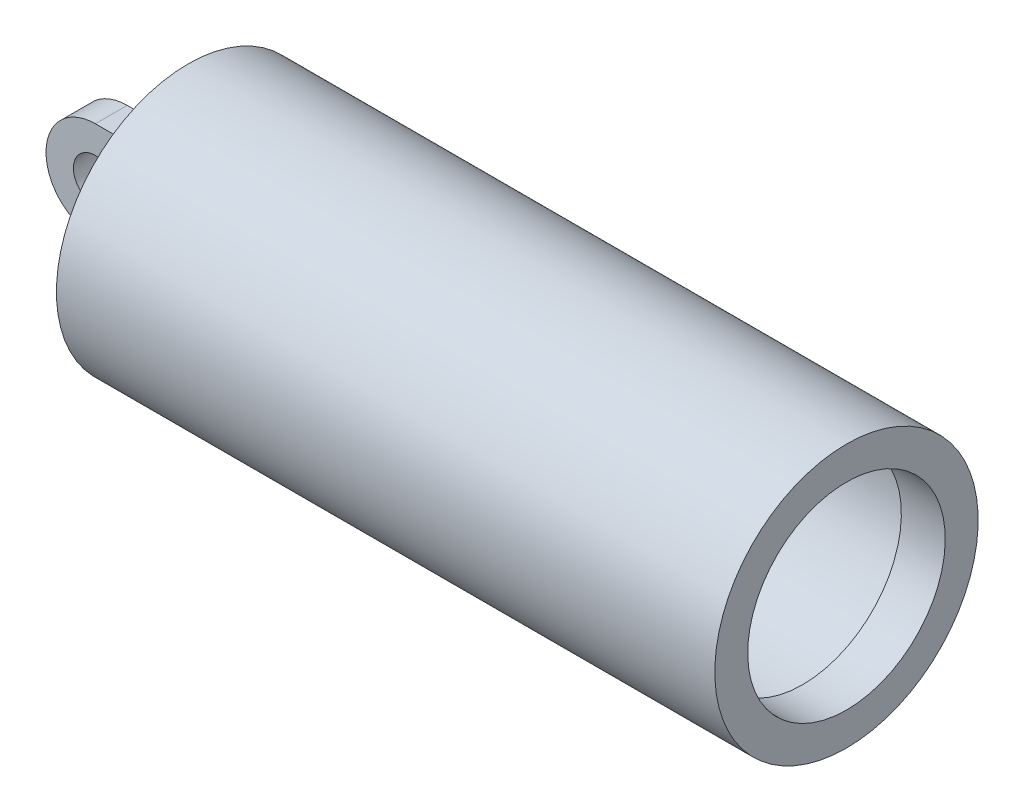
SolidWorks part; units mm, degrees
ref_plane "Front Plane" through (0, 0, 0) normal (0, 0, 1) x (1, 0, 0)
ref_plane "Top Plane" through (0, 0, 0) normal (0, 1, 0) x (1, 0, 0)
ref_plane "Right Plane" through (0, 0, 0) normal (1, 0, 0) x (0, 0, -1)
sketch "Sketch1" plane through (0, 0, 0) normal (0, 0, 1) x (1, 0, 0)
  line L2 (150, 45) -> (150, 60)
  line L3 (150, 60) -> (-150, 60)
  line L4 (-150, 60) -> (-150, 0)
  line L7 (-150, 0) -> (-130, 0)
  line L8 (-130, 0) -> (-130, 55)
  line L9 (-130, 55) -> (130, 55)
  line L10 (130, 55) -> (130, 45)
  line L11 (130, 45) -> (150, 45)
  line L12 (-150, 0) -> (150, 0) construction
  line L13 (150, 0) -> (150, 45) construction
  point P3 (140, 45)
  point P8 (0, 0)
  dimension "D3" = 15
  dimension "D1" = 60
  dimension "D4" = 300
  dimension "D6" = 5
  dimension "D7" = 20
  dimension "D8" = 20
revolve "Revolve1" add sketch "Sketch1" angle 360 about L7
sketch "Sketch3" plane through (0, 0, 0) normal (0, 0, 1) x (1, 0, 0)
  line L0 (-150, 22.5) -> (-150, -22.5)
  line L1 (-150, -22.5) -> (-185, -22.5)
  line L2 (-150, 22.5) -> (-185, 22.5)
  line L3 (-185, 22.5) -> (-185, -22.5) construction
  line L4 (-150, 60) -> (-150, -60) construction
  arc A0 (-185, 22.5) -> (-185, -22.5) centre (-185, 0) ccw
  circle A1 centre (-185, 0) radius 10
  point P5 (-150, 0)
  dimension "D3" = 22.5
  dimension "D4" = 20
  dimension "D1" = 45
  dimension "D2" = 35
extrude "Boss-Extrude1" add sketch "Sketch3" along normal blind 7.25 and the other way blind 7.25
